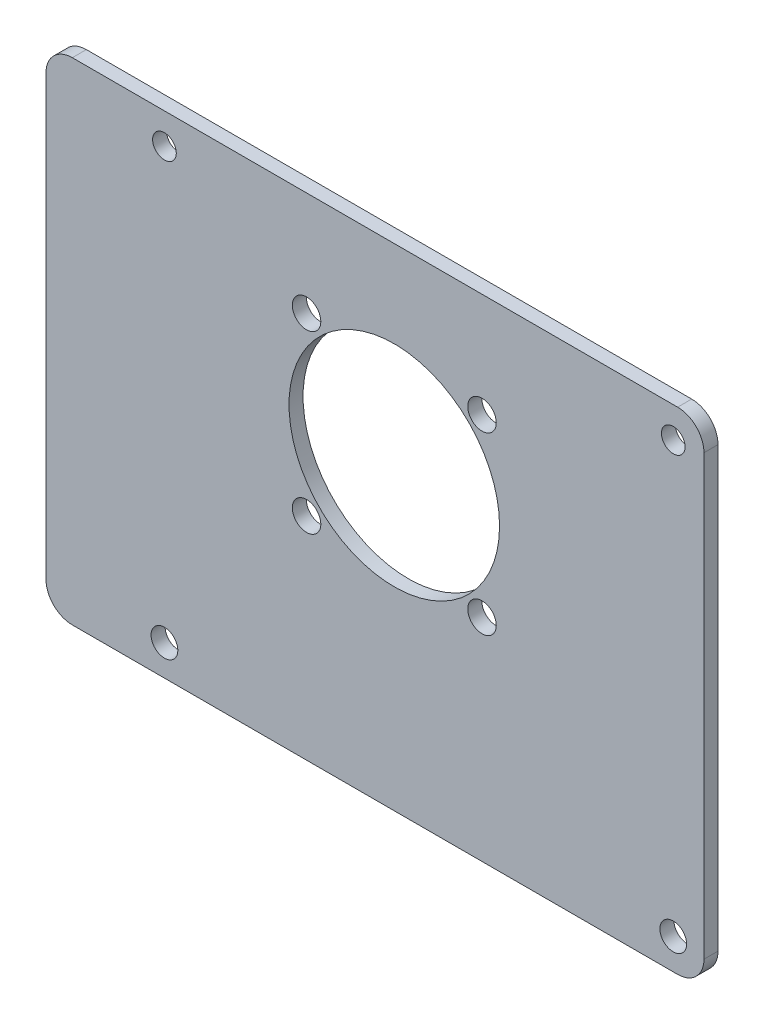
SolidWorks part; units mm, degrees
ref_plane "Front Plane" through (0, 0, 0) normal (0, 0, 1) x (1, 0, 0)
ref_plane "Top Plane" through (0, 0, 0) normal (0, 1, 0) x (1, 0, 0)
ref_plane "Right Plane" through (0, 0, 0) normal (1, 0, 0) x (0, 0, -1)
sketch "Sketch1" plane through (0, 0, 0) normal (0, 0, 1) x (1, 0, 0)
  line L0 (22.5, 25) -> (22.5, -25)
  line L1 (19, 24.5) -> (19.5, 25) construction
  line L2 (39.5, 28) -> (-39.5, 28) construction
  line L4 (42.5, -25) -> (42.5, 25)
  line L5 (39.5, 28) -> (-39.5, 28)
  line L6 (-42.5, 25) -> (-42.5, -25)
  line L7 (-39.5, -28) -> (39.5, -28)
  line L9 (19.5, 28) -> (-39.5, 28)
  line L10 (-42.5, 25) -> (-42.5, -25)
  line L11 (-39.5, -28) -> (19.5, -28)
  arc A0 (22.5, 25) -> (19.5, 28) centre (19.5, 25) ccw
  arc A1 (22.5, -25) -> (19.5, -28) centre (19.5, -25) cw
  circle A2 centre (19, 24.5) radius 1.35 construction
  circle A3 centre (-39, 24.5) radius 1.35 construction
  arc A4 (42.5, 25) -> (39.5, 28) centre (39.5, 25) ccw
  arc A5 (-39.5, 28) -> (-42.5, 25) centre (-39.5, 25) ccw
  arc A6 (-42.5, -25) -> (-39.5, -28) centre (-39.5, -25) ccw
  arc A7 (39.5, -28) -> (42.5, -25) centre (39.5, -25) ccw
  arc A9 (-39.5, 28) -> (-42.5, 25) centre (-39.5, 25) ccw
  arc A10 (-42.5, -25) -> (-39.5, -28) centre (-39.5, -25) ccw
  circle A11 centre (-39, -24.5) radius 1.524 construction
  circle A12 centre (19, -24.5) radius 1.524 construction
  circle A13 centre (-39, 24.5) radius 1.35
  circle A14 centre (-39, -24.5) radius 1.524
  circle A15 centre (19, -24.5) radius 1.524
  circle A16 centre (19, 24.5) radius 1.35
  point P18 (19, 24.5)
  dimension "D2" = 45
  dimension "D1" = 0
extrude "Boss-Extrude1" add sketch "Sketch1" along normal mid plane 1.6
sketch "Sketch2" plane through (0, 0, 0.8) normal (0, 0, 1) x (1, 0, 0)
  circle A0 centre (-2.7999, 16.11) radius 1.625
  circle A1 centre (-22.7999, 16.11) radius 1.625
  circle A2 centre (-22.7999, -3.89) radius 1.625
  circle A3 centre (-2.7999, -3.89) radius 1.625
  circle A4 centre (-12.7999, 6.11) radius 12
  dimension "D1" = 3.25
  dimension "D2" = 24
extrude "Cut-Extrude1" cut sketch "Sketch2" against normal through all
sketch "Sketch3" plane through (0, 0, 0.8) normal (0, 0, 1) x (1, 0, 0)
  line L4 (-42.5, 25) -> (-42.5, -25)
  line L5 (-39.5, -28) -> (19.5, -28)
  line L6 (22.5, -25) -> (22.5, 25)
  line L7 (19.5, 28) -> (-39.5, 28)
  line L8 (-42.5, 25) -> (-42.5, -25)
  line L9 (-39.5, -28) -> (19.5, -28)
  line L10 (22.5, -25) -> (22.5, 25)
  line L11 (19.5, 28) -> (-39.5, 28)
  arc A4 (-39.5, 28) -> (-42.5, 25) centre (-39.5, 25) ccw
  arc A5 (-42.5, -25) -> (-39.5, -28) centre (-39.5, -25) ccw
  arc A6 (19.5, -28) -> (22.5, -25) centre (19.5, -25) ccw
  arc A7 (22.5, 25) -> (19.5, 28) centre (19.5, 25) ccw
  arc A8 (-39.5, 28) -> (-42.5, 25) centre (-39.5, 25) ccw
  arc A9 (-42.5, -25) -> (-39.5, -28) centre (-39.5, -25) ccw
  arc A10 (19.5, -28) -> (22.5, -25) centre (19.5, -25) ccw
  arc A11 (22.5, 25) -> (19.5, 28) centre (19.5, 25) ccw
  point P0 (14.18, 25.89)
  point P2 (-12.7999, 6.11)
  point P7 (19, -24.5)
  point P12 (19, 24.5)
  point P15 (-39, 24.5)
  point P17 (-39, -24.5)
  dimension "D5" = 35.2999
  dimension "D2" = 3
  dimension "D3" = 59
  dimension "D4" = 53
  dimension "D6" = 34.11
  dimension "D7" = 53.89
  dimension "D8" = 8.32
  dimension "D1" = 0
sketch "Sketch4" plane through (0, 0, 0.8) normal (0, 0, 1) x (1, 0, 0)
  line L1 (-49.5, 28) -> (-39.5, 28)
  line L2 (-52.5, 25) -> (-52.5, -25)
  line L3 (-49.5, -28) -> (-39.5, -28)
  line L4 (-39.5, 28) -> (-39.5, -28)
  line L5 (-52.5, 28) -> (-39.5, -28) construction
  line L6 (-52.5, -28) -> (-39.5, 28) construction
  line L8 (19.5, 28) -> (-39.5, 28) construction
  arc A0 (-52.5, -25) -> (-49.5, -28) centre (-49.5, -25) ccw
  arc A1 (-49.5, 28) -> (-52.5, 25) centre (-49.5, 25) ccw
  arc A2 (-39.5, 28) -> (-42.5, 25) centre (-39.5, 25) ccw construction
  point P0 (-46, 0)
  arc M14 (-39.5, 28) -> (-42.5, 25) centre (-39.5, 25) ccw
  line M15 (-42.5, 25) -> (-42.5, -25)
  arc M16 (-42.5, -25) -> (-39.5, -28) centre (-39.5, -25) ccw
  dimension "D3" = 13
extrude "Boss-Extrude2" add sketch "Sketch4" against normal up to surface (1.6 mm away) contours L1 A1 L2 A0 L3 M16 M15 M14 region at (-47.431, 0, 0.8) up to face at (-21.1749, 16.11, -0.8)
sketch "Sketch5" plane through (0, 0, 0.8) normal (0, 0, 1) x (1, 0, 0)
  line L0 (-49.5, -28) -> (19.5, -28) construction
  line L1 (-11.0697, -18.8) -> (-21.2697, -18.8)
  line L2 (-11.3197, -19.05) -> (-11.3197, -28)
  line L3 (-11.3197, -28) -> (-21.0197, -28)
  line L4 (-21.0197, -19.05) -> (-21.0197, -28)
  line L5 (-11.3197, -18.8) -> (-21.0197, -28) construction
  line L6 (-11.3197, -28) -> (-21.0197, -18.8) construction
  line L7 (-13.6697, -19.8) -> (-18.6697, -19.8) construction
  line L12 (-24.0697, -18.8) -> (-32.6447, -18.8) construction
  line L13 (-23.8197, -28) -> (-34.5197, -28)
  line L20 (-12.4697, -19.8) -> (-14.8697, -19.8) construction
  line L21 (-17.4697, -19.8) -> (-19.8697, -19.8) construction
  line L22 (-11.0697, -29.5) -> (-11.0697, -18.8) construction
  line L24 (-11.0697, -18.8) -> (-19.6447, -18.8) construction
  line L25 (-23.8197, -28) -> (-23.8197, -19.05)
  line L26 (-24.0697, -18.8) -> (-34.2697, -18.8)
  line L27 (-34.5197, -28) -> (-34.5197, -19.05)
  line L28 (-23.8197, -28) -> (-34.5197, -18.8) construction
  line L29 (-23.8197, -18.8) -> (-34.5197, -28) construction
  line L30 (-14.2697, -18.8) -> (-14.2697, -15.8) construction
  line L31 (-14.9697, -18.8) -> (-14.9697, -15.8)
  line L32 (-13.5697, -18.8) -> (-13.5697, -15.8)
  line L33 (-13.6697, -15.8) -> (-14.8697, -15.8) construction
  line L34 (-13.6697, -15.8) -> (-14.8697, -15.8)
  line L35 (-14.9697, -18.14) -> (-13.6697, -18.14)
  line L36 (-13.9197, -18.39) -> (-13.9197, -18.8)
  line L37 (-12.4697, -18.14) -> (-13.6697, -18.14) construction
  line L38 (-12.4697, -18.14) -> (-13.6697, -18.14)
  line L39 (-16.1697, -19.8) -> (-16.1697, -23.4) construction
  line L40 (-18.0697, -18.8) -> (-18.0697, -15.8) construction
  line L41 (-17.3697, -18.8) -> (-17.3697, -15.8)
  line L42 (-18.7697, -18.8) -> (-18.7697, -15.8)
  line L43 (-18.4197, -18.39) -> (-18.4197, -18.8)
  line L44 (-17.3697, -18.14) -> (-18.6697, -18.14)
  line L82 (-11.3197, -28) -> (-11.3197, -29)
  line L83 (-11.0697, -29.25) -> (-21.2697, -29.25)
  line L84 (-21.0197, -29) -> (-21.0197, -28)
  line L85 (-11.0697, -29.5) -> (-19.6447, -29.5) construction
  line L86 (-34.5197, -28) -> (-34.5197, -28.2)
  line L87 (-34.2697, -28.45) -> (-24.0697, -28.45)
  line L88 (-23.8197, -28.2) -> (-23.8197, -28)
  line L89 (-31.6697, -28.2) -> (-29.6836, -28.2) construction
  arc A0 (-14.9697, -18.8) -> (-13.5697, -18.8) centre (-14.2697, -18.8) ccw
  arc A1 (-13.5697, -15.8) -> (-14.9697, -15.8) centre (-14.2697, -15.8) ccw
  arc A2 (-13.9197, -18.39) -> (-13.6697, -18.14) centre (-13.6697, -18.39) cw
  arc A3 (-17.3697, -18.8) -> (-18.7697, -18.8) centre (-18.0697, -18.8) cw
  arc A4 (-18.7697, -15.8) -> (-17.3697, -15.8) centre (-18.0697, -15.8) cw
  arc A5 (-18.4197, -18.39) -> (-18.6697, -18.14) centre (-18.6697, -18.39) ccw
  arc A6 (-23.8197, -19.05) -> (-24.0697, -18.8) centre (-24.0697, -19.05) ccw
  arc A7 (-34.2697, -18.8) -> (-34.5197, -19.05) centre (-34.2697, -19.05) ccw
  arc A8 (-21.2697, -18.8) -> (-21.0197, -19.05) centre (-21.2697, -19.05) cw
  arc A9 (-11.0697, -18.8) -> (-11.3197, -19.05) centre (-11.0697, -19.05) ccw
  arc A26 (-21.2697, -29.25) -> (-21.0197, -29) centre (-21.2697, -29) ccw
  arc A27 (-11.3197, -29) -> (-11.0697, -29.25) centre (-11.0697, -29) ccw
  arc A28 (-24.0697, -28.45) -> (-23.8197, -28.2) centre (-24.0697, -28.2) ccw
  arc A29 (-34.5197, -28.2) -> (-34.2697, -28.45) centre (-34.2697, -28.2) ccw
  point P0 (-16.1697, -23.4)
  point P9 (-29.1697, -23.4)
  point P21 (-16.1697, -19.8)
  point P32 (-14.2697, -17.3)
  point P49 (-18.0697, -17.3)
  dimension "D5" = 0.25
  dimension "D6" = 0.25
  dimension "D15" = 0.25
  dimension "D18" = 0.25
  dimension "D1" = 0.25
  dimension "D2" = 13
  dimension "D3" = 0.1
  dimension "D4" = 0.1
  dimension "D16" = 0.25
  dimension "D17" = 0.25
  dimension "D21" = 10.45
  dimension "D22" = 4.5
  dimension "D23" = 2.4
  dimension "D24" = 5.2
  dimension "D25" = 9.65
